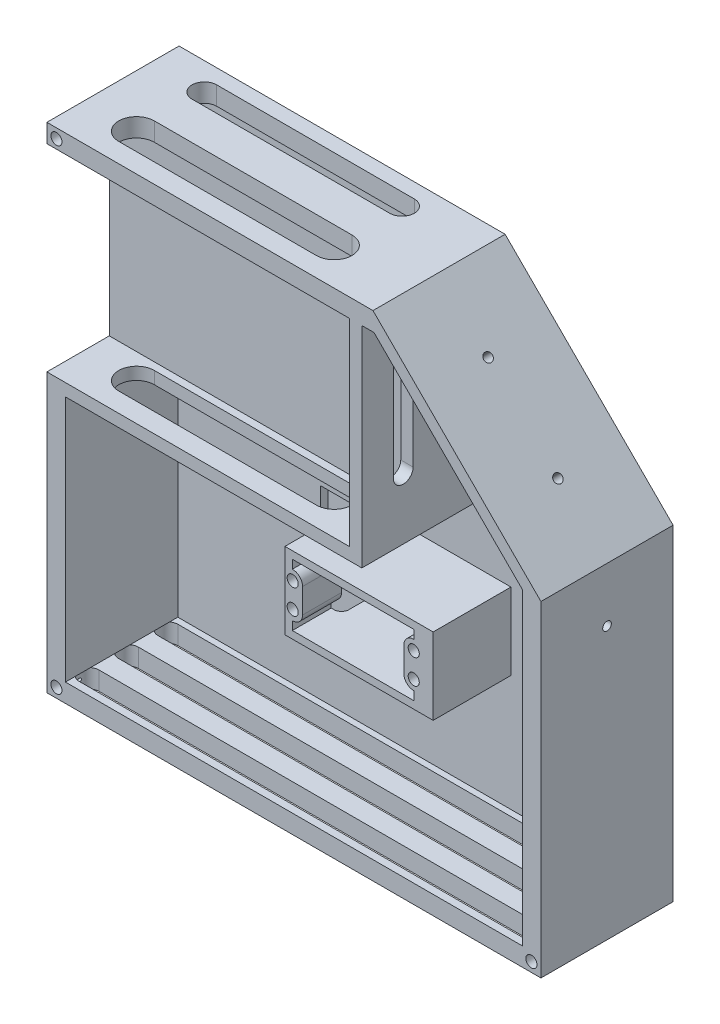
SolidWorks part; units mm, degrees
material "PEI"
ref_plane "Ground" through (0, 0, 0) normal (0, 0, 1) x (1, 0, 0)
ref_plane "Right" through (0, 0, 0) normal (0, 1, 0) x (1, 0, 0)
ref_plane "Front" through (0, 0, 0) normal (1, 0, 0) x (0, 0, -1)
sketch "Sketch1" plane through (0, 0, 0) normal (0, 0, 1) x (1, 0, 0)
  line L0 (27.5, 92.5) -> (27.5, 7.5)
  line L1 (-100, -100) -> (100, -100)
  line L2 (-100, -100) -> (-100, 100)
  line L3 (-100, 100) -> (100, 100)
  line L4 (100, -100) -> (100, 100)
  line L5 (-92.5, -92.5) -> (92.5, -92.5)
  line L6 (-92.5, -92.5) -> (-92.5, 7.5)
  line L11 (-92.5, 92.5) -> (22.5, 92.5)
  line L12 (92.5, -92.5) -> (92.5, 92.5)
  line L17 (-92.5, -92.5) -> (92.5, 92.5) construction
  line L18 (-92.5, 92.5) -> (92.5, -92.5) construction
  line L19 (-92.5, 92.5) -> (22.5, 92.5)
  line L21 (-92.5, 12.5) -> (22.5, 12.5)
  line L22 (22.5, 92.5) -> (22.5, 12.5)
  line L23 (27.5, 7.5) -> (-92.5, 7.5)
  line L24 (27.5, 92.5) -> (92.5, 92.5)
  line L25 (27.5, 92.5) -> (22.5, 92.5)
  line L26 (-92.5, 92.5) -> (-100, 92.5)
  line L27 (-92.5, 12.5) -> (-92.5, 7.5)
  line L28 (-92.5, 12.5) -> (-100, 12.5)
  line L29 (32, 100) -> (100, 32)
  line L30 (32.4289, 92.5) -> (92.5, 32.4289)
  circle A0 centre (0, -30) radius 70 construction
  point P0 (0, 0)
  point P6 (0, 0)
  point P7 (0, 0)
  point P15 (0, -100)
  point P16 (0, -92.5)
  point P17 (100, 0)
  point P18 (92.5, 0)
  dimension "D4" = 140
  dimension "D5" = 7.5
  dimension "D1" = 200
  dimension "D2" = 200
  dimension "D3" = 130
  dimension "D6" = 115
  dimension "D7" = 7.5
  dimension "D8" = 80
  dimension "D9" = 5
  dimension "D10" = 132
  dimension "D11" = 45
  dimension "D12" = 5
extrude "Boss-Extrude1" add sketch "Sketch1" along normal blind 8 contours L24 L0 L23 L6 L5 L12 | L28 L21 L22 L11 L26 L2 region at (9.0336, -28.8364, 0) region at (-38.75, 52.5, 0)
extrude "Boss-Extrude2" add sketch "Sketch1<4>" along normal blind 53.5 contours L27 L28 L2 L1 L4 L3 L26 L11 L25 L24 L12 L5 L6 | L21 L27 L23 L0 L25 L22 | L24 L30 L12 L29 | L29 L3 L2 L26 L11 L25 L24 region at (-32.1077, 96.2155, 0) region at (26.0295, 50, 0) region at (64.1954, 64.1954, 0) region at (-94.9384, -42.5, 0)
sketch "Sketch1<4>" plane through (0, 0, 0) normal (0, 0, 1) x (1, 0, 0) same geometry as "Sketch1"
sketch "Sketch9" plane through (0, -100, 0) normal (0, -1, 0) x (1, 0, 0)
  line L0 (-90, 46.4663) -> (90, 46.4663) construction
  line L1 (-90, 50.4663) -> (90, 50.4663)
  line L2 (-90, 42.4663) -> (90, 42.4663)
  line L3 (-90, 30.4663) -> (90, 30.4663) construction
  line L4 (-100, 0) -> (100, 0)
  line L5 (100, 0) -> (100, 53.5)
  line L6 (100, 53.5) -> (-100, 53.5)
  line L7 (-100, 53.5) -> (-100, 0)
  line L8 (-100, 0) -> (100, 0)
  line L10 (100, 53.5) -> (-100, 53.5)
  line L11 (-100, 53.5) -> (-100, 0)
  line L12 (-90, 34.4663) -> (90, 34.4663)
  line L13 (-90, 26.4663) -> (90, 26.4663)
  line L14 (-90, 14.4663) -> (90, 14.4663) construction
  line L15 (-90, 18.4663) -> (90, 18.4663)
  line L16 (-90, 10.4663) -> (90, 10.4663)
  line L17 (0, 50.4663) -> (0, 10.4663) construction
  line L23 (100, 0) -> (100, 53.5)
  arc A0 (-90, 50.4663) -> (-90, 42.4663) centre (-90, 46.4663) ccw
  arc A1 (90, 42.4663) -> (90, 50.4663) centre (90, 46.4663) ccw
  arc A2 (-90, 34.4663) -> (-90, 26.4663) centre (-90, 30.4663) ccw
  arc A3 (90, 26.4663) -> (90, 34.4663) centre (90, 30.4663) ccw
  arc A4 (-90, 18.4663) -> (-90, 10.4663) centre (-90, 14.4663) ccw
  arc A5 (90, 10.4663) -> (90, 18.4663) centre (90, 14.4663) ccw
  point P6 (0, 46.4663)
  point P12 (0, 30.4663)
  point P19 (0, 14.4663)
  point P32 (0, 30.4663)
  dimension "D3" = 4
  dimension "D2" = 180
  dimension "D4" = 40
  dimension "D1" = 0
extrude "Cut-Extrude6" cut sketch "Sketch9" along direction (0, 1, 0) on the side against the normal up to surface (7.5 mm away) contours L2 A1 L1 A0 | L13 A3 L12 A2 | L16 A5 L15 A4 | L2 A1 L1 A0 region at (0, -100, 46.4663) region at (0, -100, 30.4663) region at (0, -100, 14.4663) up to face at (0, -92.5, 30.75)
sketch "Sketch2" plane through (0, 0, 8) normal (0, 0, 1) x (1, 0, 0)
  line L1 (-38.4139, -30) -> (-17.6409, -30) construction
  line L2 (-14.5, -25) -> (-14.5, -30) construction
  line L3 (-14.5, -35) -> (-14.5, -30) construction
  line L4 (-14.5, -35) -> (-14.5, -25) construction
  line L6 (32.4289, 92.5) -> (27.5, 92.5)
  line L8 (32.4289, 92.5) -> (27.5, 92.5)
  line L10 (27.5, 92.5) -> (27.5, 7.5)
  line L18 (-10.5, -35) -> (-10.5, -25)
  line L19 (10.5, -12.2701) -> (10.5, -47.7299) construction
  line L20 (10, -12.2701) -> (10, -47.7299) construction
  line L21 (-14.6409, -42.5) -> (39.3591, -42.5)
  line L22 (-14.6409, -42.5) -> (-14.6409, -37.2456)
  line L23 (-14.6409, -17.5) -> (39.3591, -17.5)
  line L25 (-14.6409, -42.5) -> (39.3591, -17.5) construction
  line L26 (-14.6409, -17.5) -> (39.3591, -42.5) construction
  line L27 (-18.5, -30) -> (59.4139, -30) construction
  line L28 (-17.6409, -14.5) -> (42.3591, -14.5)
  line L29 (-17.6409, -14.5) -> (-17.6409, -45.5)
  line L30 (-17.6409, -45.5) -> (42.3591, -45.5)
  line L31 (42.3591, -14.5) -> (42.3591, -45.5)
  line L32 (-14.6409, -32.7544) -> (-14.6409, -27.2456)
  line L33 (-14.6409, -22.7544) -> (-14.6409, -17.5)
  line L34 (34.6409, -22.7544) -> (34.6409, -17.5)
  line L35 (34.6409, -32.7544) -> (34.6409, -27.2456)
  line L36 (34.6409, -42.5) -> (34.6409, -37.2456)
  line L37 (30.5, -35) -> (30.5, -25)
  line L38 (27.5, 92.5) -> (27.5, 7.5) construction
  line L39 (27.5, 92.5) -> (32.4289, 92.5) construction
  line L40 (-100, 100) -> (32, 100) construction
  line L44 (27.5, 92.5) -> (27.5, 7.5)
  line L51 (27.5, 7.5) -> (-92.5, 7.5)
  line L53 (27.5, 7.5) -> (-92.5, 7.5)
  line L56 (-92.5, 7.5) -> (-92.5, -92.5)
  line L57 (-92.5, 7.5) -> (-92.5, -92.5)
  line L58 (-92.5, -92.5) -> (92.5, -92.5)
  line L59 (-92.5, -92.5) -> (92.5, -92.5)
  line L60 (92.5, -92.5) -> (92.5, 32.4289)
  line L61 (92.5, -92.5) -> (92.5, 32.4289)
  line L62 (92.5, 32.4289) -> (32.4289, 92.5)
  line L63 (92.5, 32.4289) -> (32.4289, 92.5)
  circle A0 centre (0, -30) radius 70 construction
  circle A1 centre (-14.5, -25) radius 2.25
  circle A2 centre (-14.5, -35) radius 2.25
  arc A3 (-14.6409, -38.9975) -> (-10.5, -35) centre (-14.5, -35) ccw
  arc A4 (-10.5, -25) -> (-14.6409, -21.0025) centre (-14.5, -25) ccw
  circle A5 centre (34.5, -35) radius 2.25
  arc A6 (34.6409, -38.9975) -> (30.5, -35) centre (34.5, -35) cw
  arc A7 (30.5, -25) -> (34.6409, -21.0025) centre (34.5, -25) cw
  circle A8 centre (34.5, -25) radius 2.25
  point P11 (0, -30)
  point P19 (-14.5, -30)
  point P27 (12.3591, -30)
  point P38 (12.3591, -14.5)
  point P39 (12.3591, -17.5)
  point P40 (-17.6409, -30)
  point P41 (42.3591, -30)
  dimension "D2" = 140
  dimension "D4" = 4.5
  dimension "D7" = 4
  dimension "D3" = 130
  dimension "D5" = 5
  dimension "D6" = 14.5
  dimension "D8" = 10.5
  dimension "D9" = 54
  dimension "D10" = 25
  dimension "D11" = 0.5
  dimension "D12" = 3
  dimension "D13" = 3
  dimension "D1" = 0
extrude "Boss-Extrude3" add sketch "Sketch2" along normal blind 31.5 contours L31 L28 L29 L30 L34 A8 L35 A5 L36 L21 L22 A2 L32 A1 L33 L23 | L18 A4 L33 A1 L32 A2 L22 A3 | L35 A8 L34 A7 L37 A6 L36 A5 region at (-12.3734, -30, 8) region at (32.3734, -30, 8) region at (12.3591, -15.1754, 8)
sketch "Sketch8" plane through (-17.6409, 0, 0) normal (-1, 0, 0) x (0, 0, 1)
  line L1 (23.75, -14.5) -> (8, -14.5)
  line L2 (23.75, -14.5) -> (23.75, -45.5)
  line L3 (23.75, -45.5) -> (8, -45.5)
  line L4 (8, -14.5) -> (8, -45.5)
  line L5 (8, -45.5) -> (39.5, -45.5)
  line L6 (39.5, -45.5) -> (39.5, -14.5)
  line L7 (39.5, -14.5) -> (8, -14.5)
  line L10 (39.5, -45.5) -> (39.5, -14.5)
  line L11 (39.5, -14.5) -> (8, -14.5)
  line L12 (8, -14.5) -> (8, -45.5)
  line L16 (8, -45.5) -> (39.5, -45.5)
  line L17 (8, -14.5) -> (8, -45.5)
  line M5 (8, -14.5) -> (8, -45.5)
  line M6 (8, -45.5) -> (39.5, -45.5)
  line M8 (39.5, -14.5) -> (8, -14.5)
  dimension "D1" = 0
extrude "Cut-Extrude5" cut sketch "Sketch8" against normal up to surface (7.1409 mm away) contours L2 M8 M5 M6 region at (-17.6409, -30, 15.875) up to face at (-10.5, -30, 23.75)
sketch "Sketch10" plane through (0, 0, 8) normal (0, 0, 1) x (1, 0, 0)
  line L1 (-14.6409, -42.5) -> (34.6409, -42.5) construction
  line L4 (-14.6409, -17.5) -> (34.6409, -17.5) construction
  line L5 (34.6409, -21.0025) -> (34.6409, -17.5) construction
  line L6 (30.5, -35) -> (30.5, -25) construction
  line L7 (34.6409, -42.5) -> (34.6409, -38.9975) construction
  line L8 (34.6409, -42.5) -> (34.6409, -38.9975)
  line L9 (30.5, -35) -> (30.5, -25)
  line L10 (34.6409, -21.0025) -> (34.6409, -17.5)
  line L11 (-14.6409, -17.5) -> (34.6409, -17.5)
  line L14 (-14.6409, -42.5) -> (34.6409, -42.5)
  line L16 (-14.6409, -17.5) -> (-34.6409, -17.5)
  line L17 (-14.6409, -42.5) -> (-34.6409, -42.5)
  line L18 (-34.6409, -42.5) -> (-34.6409, -17.5)
  arc A2 (34.6409, -21.0025) -> (30.5, -25) centre (34.5, -25) ccw construction
  arc A3 (30.5, -35) -> (34.6409, -38.9975) centre (34.5, -35) ccw construction
  arc A4 (30.5, -35) -> (34.6409, -38.9975) centre (34.5, -35) ccw
  arc A5 (34.6409, -21.0025) -> (30.5, -25) centre (34.5, -25) ccw
  dimension "D1" = 20
extrude "Cut-Extrude8" cut sketch "Sketch10" against normal blind 3
fillet "Fillet1" radius 3 2 edges at (-10.5, -44, 23.75) (-10.5, -16, 23.75)
sketch "Sketch3" plane through (22.5, 0, 0) normal (-1, 0, 0) x (0, 0, 1)
  line L0 (3, 12.5) -> (53.5, 12.5)
  line L1 (28.25, 12.5) -> (28.25, 102.5) construction
  line L4 (53.5, 92.5) -> (8, 92.5)
  line L5 (8, 92.5) -> (8, 12.5)
  line L6 (8, 12.5) -> (53.5, 12.5)
  line L7 (53.5, 12.5) -> (53.5, 92.5)
  line L10 (8, 12.5) -> (53.5, 12.5) construction
  line L11 (53.5, 12.5) -> (53.5, 92.5)
  line L14 (8, 92.5) -> (3, 92.5)
  line L16 (8, 12.5) -> (3, 12.5)
  line L17 (3, 92.5) -> (3, 12.5)
  line L18 (3, 52.5) -> (53.5, 52.5) construction
  line L19 (29.75, 102.5) -> (26.75, 102.5)
  line L20 (29.75, 102.5) -> (29.75, 12.5)
  line L21 (29.75, 12.5) -> (26.75, 12.5)
  line L22 (26.75, 102.5) -> (26.75, 12.5)
  line L25 (10, 72.5) -> (10, 32.5) construction
  line L26 (14, 72.5) -> (14, 32.5)
  line L27 (6, 72.5) -> (6, 32.5)
  line L28 (36.75, 72.5) -> (36.75, 32.5) construction
  line L29 (40.75, 72.5) -> (40.75, 32.5)
  line L30 (32.75, 72.5) -> (32.75, 32.5)
  line L33 (8, 92.5) -> (3, 92.5)
  line L35 (8, 12.5) -> (3, 12.5)
  line L36 (3, 92.5) -> (3, 12.5)
  line L39 (53.5, 92.5) -> (8, 92.5)
  arc A2 (14, 72.5) -> (6, 72.5) centre (10, 72.5) ccw
  arc A3 (6, 32.5) -> (14, 32.5) centre (10, 32.5) ccw
  arc A4 (40.75, 72.5) -> (32.75, 72.5) centre (36.75, 72.5) ccw
  arc A5 (32.75, 32.5) -> (40.75, 32.5) centre (36.75, 32.5) ccw
  point P10 (28.25, 102.5)
  point P17 (10, 52.5)
  point P25 (36.75, 52.5)
  dimension "D5" = 4
  dimension "D2" = 3
  dimension "D3" = 5
  dimension "D4" = 3
  dimension "D6" = 40
  dimension "D7" = 3
  dimension "D1" = 0
extrude "Cut-Extrude1" cut sketch "Sketch3" along direction (-1, 0, 0) on the side of the normal up to surface (122.5 mm away) and the other way blind 15 contours A2 L27 A3 L26 | A4 L30 A5 L29 up to face at (-100, 26.25, 28.75)
sketch "Sketch4" plane through (22.5, 0, 0) normal (-1, 0, 0) x (0, 0, 1)
  line L0 (53.5, 100) -> (0, 100) construction
  line L1 (53.5, 100) -> (0, 100)
  line L2 (26.75, 100) -> (26.75, 12.5) construction
  line L3 (53.5, 12.5) -> (8, 12.5) construction
  line L5 (25.25, 12.5) -> (28.25, 12.5)
  line L6 (25.25, 12.5) -> (25.25, 105)
  line L7 (25.25, 105) -> (28.25, 105)
  line L8 (28.25, 12.5) -> (28.25, 105)
  point P10 (26.75, 105)
  line M9 (8, 12.5) -> (53.5, 12.5)
  line M11 (53.5, 92.5) -> (8, 92.5)
  dimension "D1" = 3
extrude "Boss-Extrude5" add sketch "Sketch4" along direction (1, 0, 0) on the side of the normal up to surface (122.5 mm away) contours L2 L5 L8 M11 | L2 L7 L6 M9 region at (22.5, 52.5, 27.5) region at (22.5, 52.5, 26) up to face at (-100, 35, 21.4226)
sketch "Sketch5" plane through (-100, 0, 0) normal (-1, 0, 0) x (0, 0, 1)
  line L1 (6, 82.5) -> (6, 42.5)
  line L2 (6, 92.5) -> (3, 92.5)
  line L3 (3, 92.5) -> (3, 12.5)
  line L4 (25.25, 12.5) -> (8, 12.5) construction
  line L5 (25.25, 12.5) -> (8, 12.5)
  line L6 (8, 12.5) -> (3, 12.5)
  line L7 (6, 82.5) -> (6, 92.5)
  line L12 (6, 42.5) -> (6, 12.5)
  line L13 (3, 92.5) -> (8, 92.5)
  line L14 (8, 92.5) -> (8, 12.5)
  line L15 (6, 82.5) -> (6, 42.5)
  arc M17 (8, 29.0359) -> (6, 32.5) centre (10, 32.5) cw
  line M18 (6, 32.5) -> (6, 72.5)
  arc M19 (6, 72.5) -> (8, 75.9641) centre (10, 72.5) cw
  line M20 (8, 75.9641) -> (8, 92.5)
  line M24 (8, 12.5) -> (8, 29.0359)
extrude "Cut-Extrude2" cut sketch "Sketch5" along direction (1, 0, 0) on the side against the normal up to surface (122.5 mm away) contours L14 M19 M18 M17 | L13 L7 M19 M20 | L12 L6 M17 M24 | L12 L7 L2 L3 L6 M18 region at (-100, 83.7104, 6.9748) region at (-100, 52.5, 4.5) region at (-100, 52.5, 7.0197) region at (-100, 21.2896, 6.9748) up to face at (22.5, 52.5, 14.0625)
sketch "Sketch6" plane through (0, 7.5, 0) normal (0, -1, 0) x (1, 0, 0)
  line L0 (22.5, 25.25) -> (-100, 25.25) construction
  line L1 (-100, 25.25) -> (-100, 3) construction
  line L2 (-100, 3) -> (22.5, 3) construction
  line L3 (22.5, 3) -> (22.5, 25.25) construction
  line L4 (-100, 53.5) -> (-100, 28.25) construction
  line L5 (-100, 28.25) -> (22.5, 28.25) construction
  line L6 (22.5, 28.25) -> (22.5, 53.5) construction
  line L7 (22.5, 53.5) -> (-100, 53.5) construction
  line L8 (22.5, 25.25) -> (-100, 25.25)
  line L9 (-100, 25.25) -> (-100, 3)
  line L10 (-100, 3) -> (22.5, 3)
  line L11 (22.5, 3) -> (22.5, 25.25)
  line L12 (-100, 53.5) -> (-100, 28.25)
  line L13 (-100, 28.25) -> (22.5, 28.25)
  line L14 (22.5, 28.25) -> (22.5, 53.5)
  line L15 (22.5, 53.5) -> (-100, 53.5)
  line L16 (-38.75, 53.5) -> (-38.75, 3) construction
  line L17 (-78.75, 11) -> (1.25, 11) construction
  line L18 (-78.75, 16) -> (1.25, 16)
  line L19 (-78.75, 6) -> (1.25, 6)
  line L20 (-78.75, 38.4555) -> (1.25, 38.4555) construction
  line L21 (-78.75, 45.661) -> (1.25, 45.661)
  line L22 (-78.75, 31.25) -> (1.25, 31.25)
  arc A0 (-78.75, 16) -> (-78.75, 6) centre (-78.75, 11) ccw
  arc A1 (1.25, 6) -> (1.25, 16) centre (1.25, 11) ccw
  arc A2 (-78.75, 45.661) -> (-78.75, 31.25) centre (-78.75, 38.4555) ccw
  arc A3 (1.25, 31.25) -> (1.25, 45.661) centre (1.25, 38.4555) ccw
  point P10 (-38.75, 11)
  point P18 (-38.75, 38.4555)
  line M8 (-92.5, 8) -> (27.5, 8)
  dimension "D2" = 5
  dimension "D1" = 80
  dimension "D3" = 3
  dimension "D4" = 3
extrude "Cut-Extrude3" cut sketch "Sketch6" along direction (0, 1, 0) on the side against the normal up to surface (92.5 mm away) and the other way blind 15 contours L22 A3 L21 A2 | A1 L18 A0 M8 | L19 A1 A0 M8 region at (-38.75, 7.5, 7.0121) region at (-38.75, 7.5, 11.9651) region at (-38.75, 7.5, 38.4555) up to face at (-34, 100, 26.75)
sketch "Sketch7" plane through (0, 0, 53.5) normal (0, 0, 1) x (1, 0, 0)
  line L0 (0, 100) -> (0, -100) construction
  line L1 (-100, 100) -> (100, 100)
  line L2 (-100, 100) -> (-100, -100)
  line L3 (-100, -100) -> (100, -100)
  line L4 (100, 100) -> (100, -100)
  line L5 (-100, 100) -> (100, -100) construction
  line L6 (-100, -100) -> (100, 100) construction
  line L7 (-100, 0) -> (100, 0) construction
  circle A1 centre (-96.15, 96.15) radius 2.25
  circle A2 centre (96.15, 96.15) radius 2.25
  circle A3 centre (96.15, -96.15) radius 2.25
  circle A4 centre (-96.15, -96.15) radius 2.25
  dimension "D1" = 4.5
  dimension "D2" = 3.85
extrude "Cut-Extrude4" cut sketch "Sketch7" against normal blind 13.5 contours A1 | A2 | A4 | A3 region at (-96.15, 96.15, 53.5) region at (96.15, 96.15, 53.5) region at (96.15, -96.15, 53.5) region at (-96.15, -96.15, 53.5)
sketch "Sketch11" plane through (66, 66, 0) normal (0.7071, 0.7071, 0) x (0, 0, -1)
  line L0 (-26.75, 48.0833) -> (-26.75, -48.0833) construction
  line L4 (0, -48.0833) -> (0, 48.0833)
  line L5 (0, 48.0833) -> (-53.5, 48.0833)
  line L6 (-53.5, 48.0833) -> (-53.5, -48.0833)
  line L7 (-53.5, -48.0833) -> (0, -48.0833)
  line L8 (0, -48.0833) -> (0, 48.0833)
  line L9 (0, 48.0833) -> (-53.5, 48.0833)
  line L10 (-53.5, 48.0833) -> (-53.5, -48.0833)
  line L11 (-53.5, -48.0833) -> (0, -48.0833)
  circle A0 centre (-26.75, -20) radius 1.75
  circle A2 centre (-26.75, 20) radius 1.75
  point P13 (-26.75, 0)
  dimension "D2" = 3.5
  dimension "D3" = 26.75
  dimension "D4" = 20
  dimension "D1" = 0
  dimension "D5" = 2
sketch "Sketch13" plane through (100, 0, 0) normal (1, 0, 0) x (0, 0, -1)
  line L0 (-53.5, -12) -> (0, -12) construction
  line L1 (-26.75, -12) -> (-26.75, 32) construction
  line L4 (0, -100) -> (0, 32)
  line L5 (0, 32) -> (-53.5, 32)
  line L6 (-53.5, 32) -> (-53.5, -100)
  line L7 (-53.5, -100) -> (0, -100)
  line L8 (0, -100) -> (0, 32)
  line L9 (0, 32) -> (-53.5, 32)
  line L10 (-53.5, 32) -> (-53.5, -100)
  line L11 (-53.5, -100) -> (0, -100)
  circle A0 centre (-26.75, 10) radius 1.75
  dimension "D3" = 3.5
  dimension "D2" = 44
  dimension "D4" = 26.75
  dimension "D1" = 0
extrude "Cut-Extrude9" cut sketch "Sketch11" against normal up to surface (5 mm away) contours A0 L0 | L0 A0 | A2 L0 | L0 A2 region at (51.8579, 80.1421, 26.0073) region at (51.8579, 80.1421, 27.4927) region at (80.1421, 51.8579, 26.0073) region at (80.1421, 51.8579, 27.4927) up to face at (62.4645, 62.4645, 30.75)
extrude "Cut-Extrude10" cut sketch "Sketch13" along direction (-1, 0, 0) on the side against the normal up to surface (7.5 mm away) contours A0 region at (100, 10, 26.75) up to face at (92.5, -67.5142, 30.5798)
